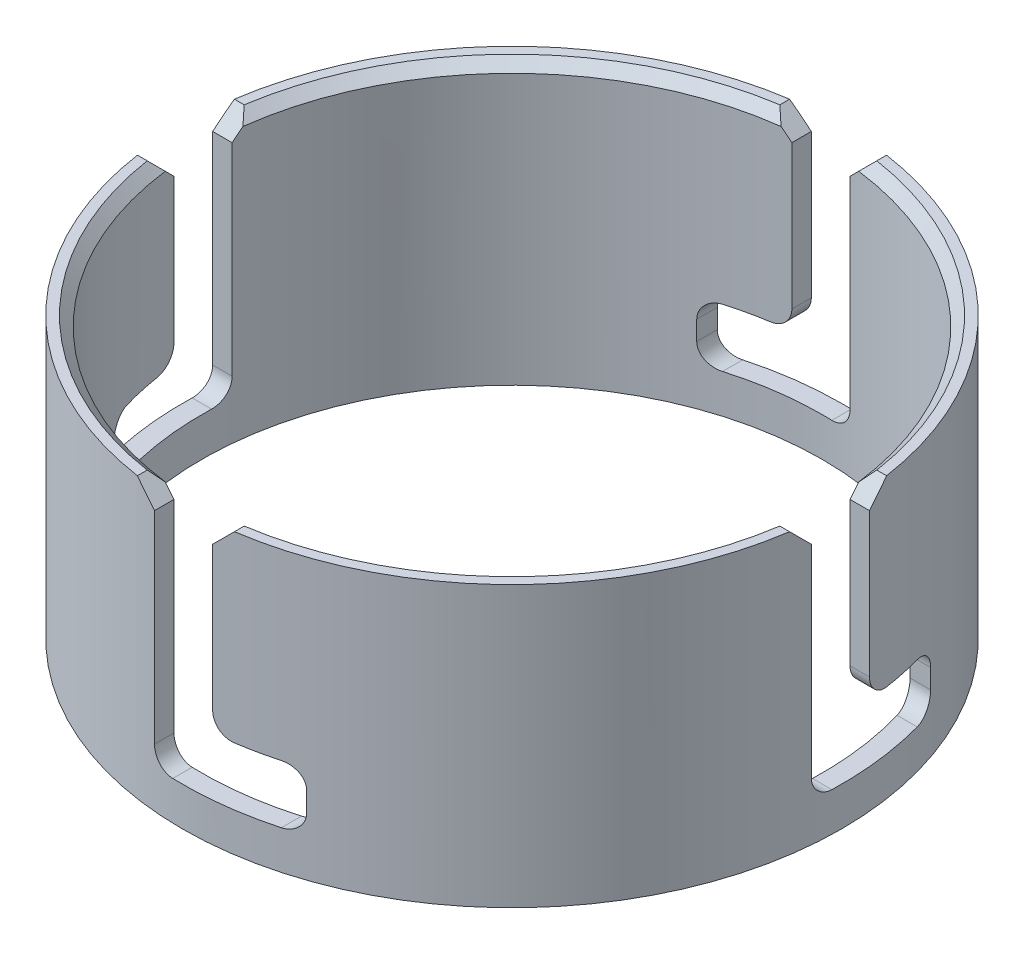
SolidWorks part; units mm, degrees
material "Plain Carbon Steel"
ref_plane "Front Plane" through (0, 0, 0) normal (0, 0, 1) x (1, 0, 0)
ref_plane "Top Plane" through (0, 0, 0) normal (0, 1, 0) x (1, 0, 0)
ref_plane "Right Plane" through (0, 0, 0) normal (1, 0, 0) x (0, 0, -1)
sketch "Sketch2" plane through (0, 0, 0) normal (1, 0, 0) x (0, 0, -1)
  line L0 (-79.9998, 0) -> (-84.9998, 0)
  line L1 (-84.9998, 0) -> (-84.9998, 72.15)
  line L2 (-84.9998, 72.15) -> (-79.9998, 72.15)
  line L5 (-79.9998, 72.15) -> (-79.9998, 0)
  dimension "D1" = 84.9998
  dimension "D2" = 72.15
  dimension "D3" = 5
ref_axis "Axis1" through (0, -3.6075, 0) along (0, 1, 0)
revolve "Revolve1" add sketch "Sketch2" angle 360 about axis through (0, -3.6075, 0) along (0, 1, 0)
sketch "Sketch3" plane through (0, 0, 0) normal (1, 0, 0) x (0, 0, -1)
  line L0 (-7.5, 72.15) -> (7.5, 72.15)
  line L1 (84.9998, 72.15) -> (-84.9998, 72.15) construction
  line L2 (7.5, 72.15) -> (7.5, 10)
  line L3 (7.5, 10) -> (-27.5, 10)
  line L4 (-27.5, 10) -> (-27.5, 25)
  line L5 (-27.5, 25) -> (-7.5, 25)
  line L6 (-7.5, 25) -> (-7.5, 72.15)
  line L7 (0, -3.6075) -> (0, 75.7575) construction
  line L8 (0, 0) -> (0, 47.5309) construction
  line L9 (-84.9998, 0) -> (84.9998, 0) construction
  dimension "D1" = 10
  dimension "D2" = 15
  dimension "D3" = 15
  dimension "D4" = 20
extrude "Cut-Extrude1" cut sketch "Sketch3" against normal through all
fillet "Fillet1" radius 5 2 edges at (-82.1579, 25, 7.5) (-82.1579, 10, -7.5)
chamfer "Chamfer1" distance 5 angle 45 2 edges at (-82.1579, 72.15, 7.5) (-82.1579, 72.15, -7.5)
fillet "Fillet3" radius 5 2 edges at (-77.7765, 25, 27.5) (-77.7765, 10, 27.5)
pattern_circular "CirPattern1" count 4 over 360 about axis through (0, -3.6075, 0) along (0, 1, 0) of "Fillet3", "Chamfer1", "Fillet1", "Cut-Extrude1"
chamfer "Chamfer2" distance 2.5 angle 45 4 edges at (-56.5684, 72.15, -56.5684) (56.5684, 72.15, -56.5684) (56.5684, 72.15, 56.5684) (-56.5684, 72.15, 56.5684)
equation "\"TubeDiameter\" = 6.6929in"
equation "\"D1@Sketch2\"=\"TubeDiameter\"/2"
